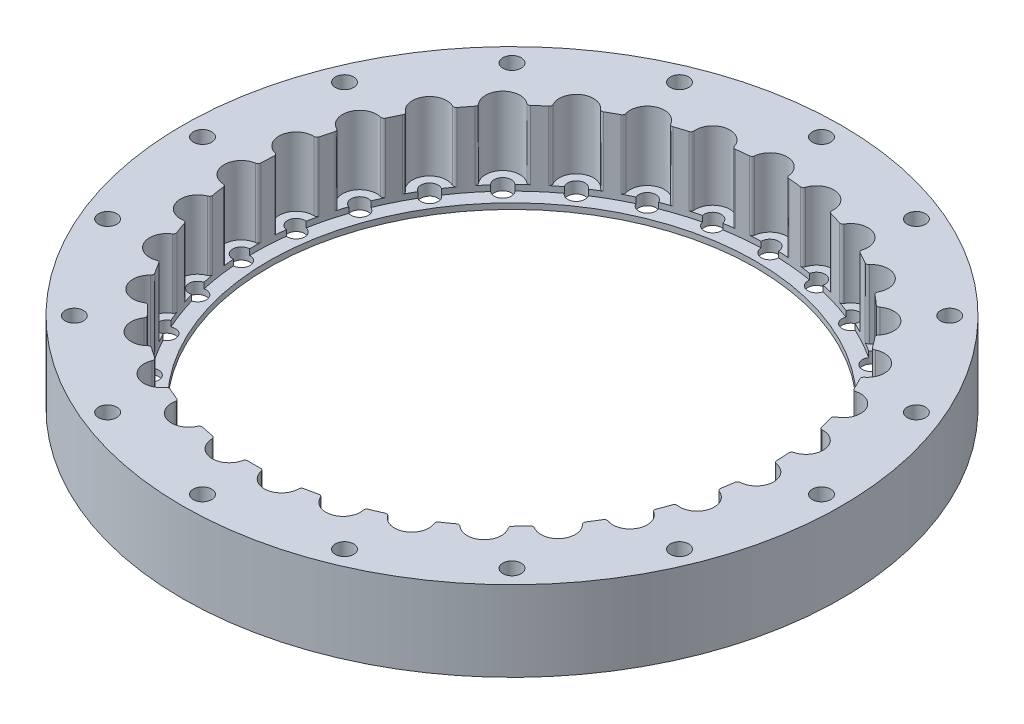
SolidWorks part; units mm, degrees
ref_plane "Front Plane" through (0, 0, 0) normal (0, 0, 1) x (1, 0, 0)
ref_plane "Top Plane" through (0, 0, 0) normal (0, 1, 0) x (1, 0, 0)
ref_plane "Right Plane" through (0, 0, 0) normal (1, 0, 0) x (0, 0, -1)
sketch "Sketch1" plane through (0, 0, 0) normal (0, 1, 0) x (1, 0, 0)
  line L0 (15.8389, 51.6249) -> (0, 0) construction
  line L1 (0, 0) -> (-4.5526, -44.7691) construction
  circle A0 centre (0, 0) radius 45
  circle A12 centre (0, 0) radius 57.5
  circle A13 centre (0, 0) radius 54 construction
  point P27 (0, 0)
  point P54 (0, 0)
  dimension "D1" = 90
  dimension "D4" = 115
  dimension "D5" = 108
  dimension "D8" = 11.25
extrude "Boss-Extrude1" add sketch "Sketch1" along normal blind 12 contours A12 region at (-55.8737, 0, 0)
sketch "Sketch2" plane through (0, 0, 0) normal (0, -1, 0) x (1, 0, 0)
  circle A0 centre (0, 0) radius 57.5
  circle A1 centre (0, 0) radius 45
extrude "Boss-Extrude2" add sketch "Sketch2" along normal blind 1
sketch "Sketch3" plane through (0, -1, 0) normal (0, -1, 0) x (1, 0, 0)
  circle A0 centre (0, 0) radius 57.5
  circle A1 centre (0, 0) radius 42.5
  dimension "D1" = 85
extrude "Boss-Extrude3" add sketch "Sketch3" along normal blind 1
sketch "Sketch5" plane through (0, 12, 0) normal (0, 1, 0) x (1, 0, 0)
  circle A0 centre (0, 45) radius 3
  circle A1 centre (0, 0) radius 45 construction
  circle A2 centre (0, 0) radius 45 construction
  dimension "D1" = 6
extrude "Cut-Extrude2" cut sketch "Sketch5" against normal blind 12
fillet "Fillet4" radius 0.5 2 edges at (2.9983, 6, -44.9) (-2.9983, 6, -44.9)
sketch "Sketch7" plane through (0, 0, 0) normal (0, 1, 0) x (1, 0, 0)
  circle A0 centre (0, 45) radius 1.5
  arc A1 (3.4425, 44.8681) -> (-3.4425, 44.8681) centre (0, 0) ccw construction
  dimension "D1" = 3
extrude "Cut-Extrude3" cut sketch "Sketch7" against normal blind 10
pattern_circular "CirPattern3" count 31 over 360 about axis through (0, -2, 0) along (0, 1, 0) of "Cut-Extrude2", "Fillet4", "Cut-Extrude3"
sketch "Sketch4" plane through (0, 12, 0) normal (0, 1, 0) x (1, 0, 0)
  circle A0 centre (0, 0) radius 54 construction
  circle A1 centre (0, 54) radius 1.6
  circle A2 centre (20.6649, 49.8895) radius 1.6
  circle A3 centre (38.1838, 38.1838) radius 1.6
  circle A4 centre (49.8895, 20.6649) radius 1.6
  circle A5 centre (54, 0) radius 1.6
  circle A6 centre (49.8895, -20.6649) radius 1.6
  circle A7 centre (38.1838, -38.1838) radius 1.6
  circle A8 centre (20.6649, -49.8895) radius 1.6
  circle A9 centre (0, -54) radius 1.6
  circle A10 centre (-20.6649, -49.8895) radius 1.6
  circle A11 centre (-38.1838, -38.1838) radius 1.6
  circle A12 centre (-49.8895, -20.6649) radius 1.6
  circle A13 centre (-54, 0) radius 1.6
  circle A14 centre (-49.8895, 20.6649) radius 1.6
  circle A15 centre (-38.1838, 38.1838) radius 1.6
  circle A16 centre (-20.6649, 49.8895) radius 1.6
  circle A17 centre (0, 0) radius 45 construction
  point P38 (0, 0)
  point P102 (0, 0)
  dimension "D1" = 108
  dimension "D2" = 3.2
extrude "Cut-Extrude1" cut sketch "Sketch4" against normal blind 51
